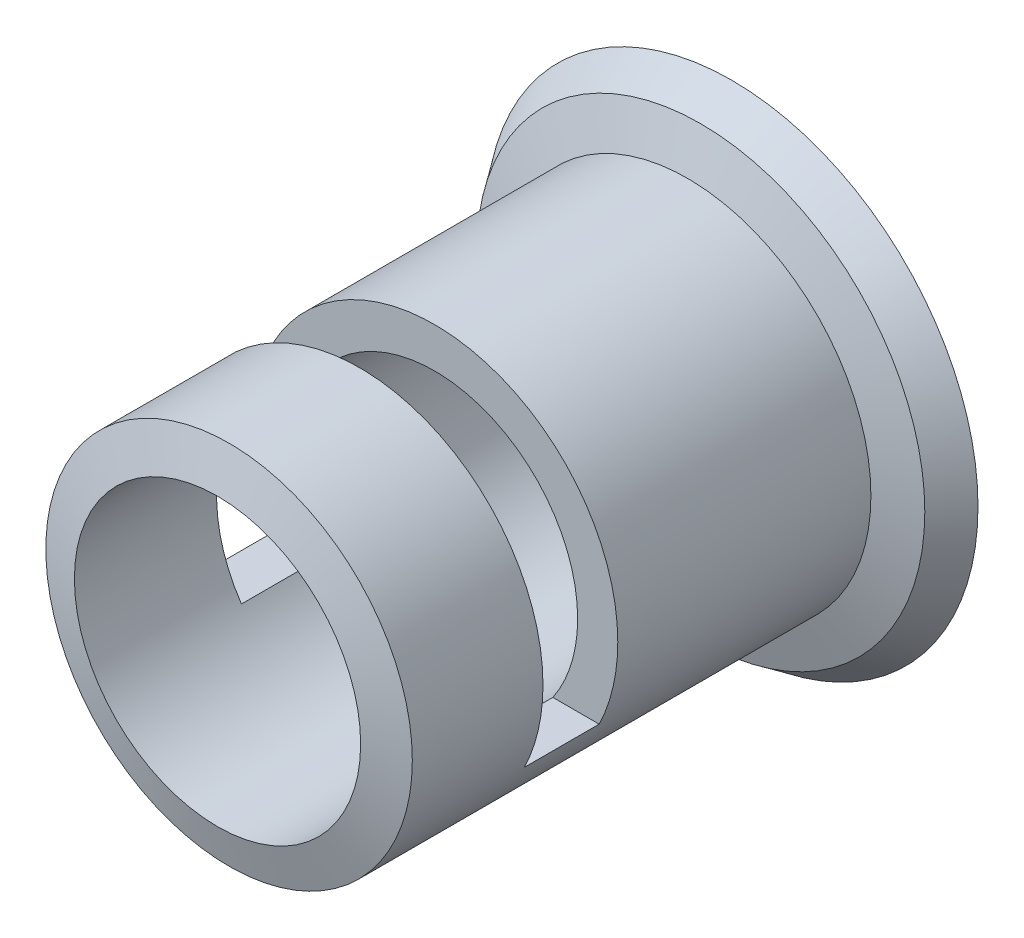
SolidWorks part; units mm, degrees
ref_plane "Front Plane" through (0, 0, 0) normal (0, 0, 1) x (1, 0, 0)
ref_plane "Top Plane" through (0, 0, 0) normal (0, 1, 0) x (1, 0, 0)
ref_plane "Right Plane" through (0, 0, 0) normal (1, 0, 0) x (0, 0, -1)
sketch "Sketch1" plane through (0, 0, 0) normal (1, 0, 0) x (0, 0, -1)
  line L0 (0, 34.9968) -> (2.825, 44.8095)
  line L1 (2.825, 44.8095) -> (114.9612, 44.8095)
  line L2 (114.9612, 44.8095) -> (118.1379, 54.8117)
  line L3 (118.1379, 54.8117) -> (125.7618, 60.195)
  line L4 (125.7618, 60.195) -> (125.7618, 34.9968)
  line L5 (125.7618, 34.9968) -> (0, 34.9968)
  line L6 (0, 0) -> (36.5551, 0) construction
  dimension "D1" = 34.9968
  dimension "D2" = 44.8095
  dimension "D3" = 2.825
  dimension "D4" = 114.9612
  dimension "D5" = 118.1379
  dimension "D6" = 54.8117
  dimension "D7" = 125.7618
  dimension "D8" = 60.195
revolve "Revolve1" add sketch "Sketch1" angle 360 about L6
sketch "Sketch2" plane through (0, 0, 0) normal (1, 0, 0) x (0, 0, -1)
  line L1 (34.7749, 52.5504) -> (53.0657, 52.5504)
  line L2 (34.7749, 52.5504) -> (34.7749, -19.6926)
  line L3 (34.7749, -19.6926) -> (53.0657, -19.6926)
  line L4 (53.0657, 52.5504) -> (53.0657, -19.6926)
  dimension "D1" = 34.7749
  dimension "D2" = 18.2908
  dimension "D3" = 19.6926
extrude "Cut-Extrude1" cut sketch "Sketch2" against normal through all and the other way through all
